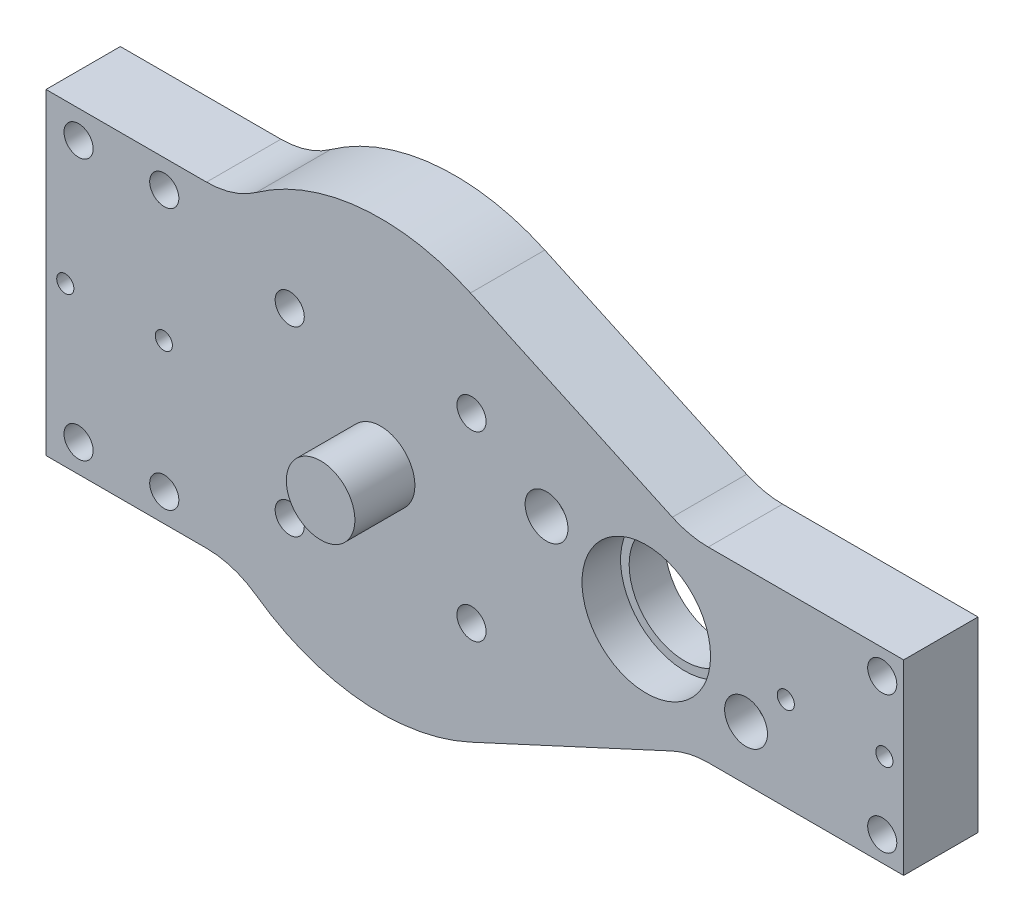
SolidWorks part; units mm, degrees
ref_plane "Front Plane" through (0, 0, 0) normal (0, 0, 1) x (1, 0, 0)
ref_plane "Top Plane" through (0, 0, 0) normal (0, 1, 0) x (1, 0, 0)
ref_plane "Right Plane" through (0, 0, 0) normal (1, 0, 0) x (0, 0, -1)
sketch "Sketch1" plane through (0, 0, 0) normal (0, 0, 1) x (1, 0, 0)
  line L0 (10.4839, 22.6956) -> (36.0323, 10.8939)
  line L1 (36.0323, -10.8939) -> (10.4839, -22.6956)
  circle A0 centre (0, 0) radius 22.215 construction
  circle A1 centre (31, 0) radius 10.2 construction
  arc A2 (10.4839, 22.6956) -> (10.4839, -22.6956) centre (0, 0) ccw
  arc A3 (36.0323, -10.8939) -> (36.0323, 10.8939) centre (31, 0) ccw
  dimension "D1" = 20.4
  dimension "D2" = 44.43
  dimension "D4" = 25
  dimension "D5" = 12
  dimension "D3" = 31
extrude "Boss-Extrude1" add sketch "Sketch1" along normal blind 4.5
sketch "Sketch2" plane through (0, 0, 4.5) normal (0, 0, 1) x (1, 0, 0)
  circle A0 centre (31, 0) radius 7.5
  dimension "D1" = 15
extrude "Cut-Extrude1" cut sketch "Sketch2" against normal through all
sketch "Sketch3" plane through (0, 0, 4.5) normal (0, 0, 1) x (1, 0, 0)
  circle A0 centre (0, 0) radius 4
  dimension "D1" = 8
extrude "Boss-Extrude2" add sketch "Sketch3" along normal blind 7
sketch "Sketch4" plane through (0, 0, 0) normal (0, 0, -1) x (-1, 0, 0)
  line L0 (-36.0323, 10.8939) -> (-56.0323, 10.8939)
  line L1 (-36.0323, -10.8939) -> (-56.0323, -10.8939)
  line L2 (-56.0323, -10.8939) -> (-56.0323, 10.8939)
  line L3 (22.5016, 10.8939) -> (42.5016, 10.8939)
  line L4 (42.5016, 10.8939) -> (42.5016, -10.8939)
  line L5 (42.5016, -10.8939) -> (22.5016, -10.8939)
  arc A0 (-10.4839, -22.6956) -> (-10.4839, 22.6956) centre (0, 0) ccw construction
  arc A1 (22.5016, -10.8939) -> (22.5016, 10.8939) centre (0, 0) ccw
  arc A2 (-36.0323, 10.8939) -> (-36.0323, -10.8939) centre (-31, 0) ccw construction
  arc A3 (-36.0323, 10.8939) -> (-36.0323, -10.8939) centre (-31, 0) ccw
  dimension "D1" = 20
  dimension "D2" = 20
extrude "Boss-Extrude3" add sketch "Sketch4" against normal up to surface (4.5 mm away) up to face at (4, 0, 4.5)
fillet "Fillet1" radius 10 4 edges at (-42.5016, 10.8939, 2.25) (-42.5016, -10.8939, 2.25) (56.0323, -10.8939, 2.25) (56.0323, 10.8939, 2.25)
sketch "Sketch8" plane through (0, 0, 4.5) normal (0, 0, 1) x (1, 0, 0)
  line L0 (56.0323, 0.8939) -> (56.0323, -0.8939) construction
  line L2 (56.0323, 0.8939) -> (56.0323, -0.8939)
  line L3 (55.4014, -4.3896) -> (55.4014, 4.3896)
  line L4 (-42.5016, -0.8939) -> (-42.5016, 0.8939) construction
  line L6 (-42.5016, -0.8939) -> (-42.5016, 0.8939)
  line L7 (-41.8707, 4.3896) -> (-41.8707, -4.3896)
  arc A0 (56.0323, 0.8939) -> (46.0323, 10.8939) centre (46.0323, 0.8939) ccw construction
  arc A1 (46.0323, -10.8939) -> (56.0323, -0.8939) centre (46.0323, -0.8939) ccw construction
  arc A2 (56.0323, 0.8939) -> (55.4014, 4.3896) centre (46.0323, 0.8939) ccw
  arc A3 (55.4014, -4.3896) -> (56.0323, -0.8939) centre (46.0323, -0.8939) ccw
  arc A4 (-32.5016, 10.8939) -> (-42.5016, 0.8939) centre (-32.5016, 0.8939) ccw construction
  arc A5 (-42.5016, -0.8939) -> (-32.5016, -10.8939) centre (-32.5016, -0.8939) ccw construction
  arc A6 (-41.8707, 4.3896) -> (-42.5016, 0.8939) centre (-32.5016, 0.8939) ccw
  arc A7 (-42.5016, -0.8939) -> (-41.8707, -4.3896) centre (-32.5016, -0.8939) ccw
extrude "Cut-Extrude4" cut sketch "Sketch8" against normal through all
sketch "Sketch9" plane through (0, 0, 4.5) normal (0, 0, 1) x (1, 0, 0)
  circle A0 centre (0, 0) radius 15 construction
  circle A1 centre (-10.6066, 10.6066) radius 1
  circle A2 centre (10.6066, 10.6066) radius 1
  circle A3 centre (10.6066, -10.6066) radius 1
  circle A4 centre (-10.6066, -10.6066) radius 1
  point P14 (0, 0)
  dimension "D1" = 30
  dimension "D2" = 2
  dimension "D3" = 4
extrude "Cut-Extrude5" cut sketch "Sketch9" against normal through all
sketch "Sketch10" plane through (0, 0, 4.5) normal (0, 0, 1) x (1, 0, 0)
  circle A0 centre (-10.6066, 10.6066) radius 1.7
  circle A1 centre (10.6066, 10.6066) radius 1.7
  circle A2 centre (10.6066, -10.6066) radius 1.7
  circle A3 centre (-10.6066, -10.6066) radius 1.7
  dimension "D1" = 3.4
extrude "Cut-Extrude6" cut sketch "Sketch10" against normal blind 2.4
sketch "Sketch11" plane through (0, 0, 0) normal (0, 0, -1) x (-1, 0, 0)
  line L0 (-40.9602, 14.6461) -> (-73.6718, 18.9155)
  line L1 (-73.6718, 18.9155) -> (-68.6403, -15.6759)
  line L2 (-68.6403, -15.6759) -> (-41.445, -13.2122)
  arc A0 (-40.9602, 14.6461) -> (-41.445, -13.2122) centre (0, 0) ccw
  dimension "D1" = 87
extrude "Cut-Extrude7" cut sketch "Sketch11" against normal up to surface (4.5 mm away) up to face at (-8.9066, -10.6066, 4.5)
fillet "Fillet2" radius 10 2 edges at (42.1138, -10.8939, 2.25) (42.1138, 10.8939, 2.25)
sketch "Sketch12" plane through (0, 0, 4.5) normal (0, 0, 1) x (1, 0, 0)
  line L0 (-22.5016, 10.8939) -> (-42.5927, 14.8195)
  line L1 (-42.5927, 14.8195) -> (-48.1481, -13.6126)
  line L2 (-48.1481, -13.6126) -> (-27.4273, -14.3153)
  line L3 (-27.4273, -14.3153) -> (-22.5016, -10.8939)
  arc A0 (-22.5016, 10.8939) -> (-22.5016, -10.8939) centre (0, 0) ccw
extrude "Cut-Extrude8" cut sketch "Sketch12" against normal through all
sketch "Sketch23" plane through (0, 0, 0) normal (0, 0, -1) x (-1, 0, 0)
  line L2 (-36.0323, -10.8939) -> (-10.4839, -22.6956)
  line L3 (-10.4839, 22.6956) -> (-36.0323, 10.8939)
  line L4 (-36.0323, -10.8939) -> (-10.4839, -22.6956)
  line L5 (-10.4839, 22.6956) -> (-36.0323, 10.8939)
  circle A0 centre (-10.6066, -10.6066) radius 1 construction
  circle A1 centre (10.6066, -10.6066) radius 1 construction
  circle A2 centre (10.6066, 10.6066) radius 1 construction
  circle A3 centre (-10.6066, 10.6066) radius 1 construction
  arc A4 (-10.4839, -22.6956) -> (-10.4839, 22.6956) centre (0, 0) ccw
  arc A5 (-36.0323, 10.8939) -> (-43.4709, 1.5916) centre (-33.4776, 1.2257) ccw
  arc A6 (-43.4709, 1.5916) -> (-43.4709, -1.5916) centre (0, 0) ccw
  arc A7 (-43.4709, -1.5916) -> (-36.0323, -10.8939) centre (-33.4776, -1.2257) ccw
  arc A8 (-10.4839, -22.6956) -> (-10.4839, 22.6956) centre (0, 0) ccw
  arc A9 (-36.0323, 10.8939) -> (-43.4709, 1.5916) centre (-33.4776, 1.2257) ccw
  arc A10 (-43.4709, 1.5916) -> (-43.4709, -1.5916) centre (0, 0) ccw
  arc A11 (-43.4709, -1.5916) -> (-36.0323, -10.8939) centre (-33.4776, -1.2257) ccw
  circle A12 centre (-10.6066, -10.6066) radius 1
  circle A13 centre (10.6066, -10.6066) radius 1
  circle A14 centre (10.6066, 10.6066) radius 1
  circle A15 centre (-10.6066, 10.6066) radius 1
  circle A16 centre (-31, 0) radius 6.5
  dimension "D2" = 13
  dimension "D1" = 0
extrude "Boss-Extrude6" add sketch "Sketch23" along normal blind 4.175
sketch "Sketch24" plane through (0, 0, -4.175) normal (0, 0, -1) x (-1, 0, 0)
  line L0 (-10.6066, 10.6066) -> (10.6066, 10.6066) construction
ref_axis "Axis1" through (10.6066, 10.6066, -4.175) along (-1, 0, 0)
sketch "Sketch25" plane through (0, 0, -4.175) normal (0, 0, -1) x (-1, 0, 0)
  line L1 (-36.0323, 10.8939) -> (-56.0323, 10.8939)
  line L3 (-36.0323, -10.8939) -> (-56.0323, -10.8939)
  line L4 (-56.0323, 10.8939) -> (-56.0323, -10.8939)
  arc A0 (-43.4709, -1.5916) -> (-36.0323, -10.8939) centre (-33.4776, -1.2257) ccw construction
  arc A1 (-43.4709, 1.5916) -> (-43.4709, -1.5916) centre (0, 0) ccw construction
  arc A2 (-36.0323, 10.8939) -> (-43.4709, 1.5916) centre (-33.4776, 1.2257) ccw construction
  arc A3 (-43.4709, -1.5916) -> (-36.0323, -10.8939) centre (-33.4776, -1.2257) ccw
  arc A4 (-43.4709, 1.5916) -> (-43.4709, -1.5916) centre (0, 0) ccw
  arc A5 (-36.0323, 10.8939) -> (-43.4709, 1.5916) centre (-33.4776, 1.2257) ccw
  dimension "D1" = 20
extrude "Boss-Extrude7" add sketch "Sketch25" against normal up to surface (8.675 mm away) up to face at (24.5985, 0, 4.5)
sketch "Sketch26" plane through (0, 0, 4.5) normal (0, 0, 1) x (1, 0, 0)
  line L0 (36.0323, 10.8939) -> (56.0323, 10.8939) construction
  line L1 (56.0323, -10.8939) -> (47.0323, -10.8939)
  line L2 (56.0323, -10.8939) -> (56.0323, 10.8939)
  line L3 (56.0323, 10.8939) -> (47.0323, 10.8939)
  line L4 (47.0323, -10.8939) -> (47.0323, 10.8939)
  dimension "D1" = 9
extrude "Boss-Extrude8" add sketch "Sketch26" along normal blind 33
sketch "Sketch27" plane through (56.0323, 0, 0) normal (1, 0, 0) x (0, 0, -1)
  circle A0 centre (-29.5, 0) radius 5
extrude "Cut-Extrude9" cut sketch "Sketch27" against normal up to next
sketch "Sketch28" plane through (0, 0, -4.175) normal (0, 0, -1) x (-1, 0, 0)
  line L1 (16.8152, 18.5) -> (52.8559, 18.5)
  line L3 (16.8152, -18.5) -> (52.8559, -18.5)
  line L4 (0, 0) -> (56, 0) construction
  line L5 (56, 0) -> (25.875, 18.5) construction
  line L6 (56, 0) -> (31.6196, -18.5) construction
  line L7 (52.8559, -18.5) -> (25, 0) construction
  line L8 (25, 0) -> (52.8559, 18.5) construction
  line L9 (52.8559, 18.5) -> (52.8559, -18.5)
  arc A0 (52.8559, -18.5) -> (52.8559, 18.5) centre (0, 0) ccw construction
  arc A2 (-10.4839, -22.6956) -> (-10.4839, 22.6956) centre (0, 0) ccw construction
  arc A3 (16.8152, -18.5) -> (16.8152, 18.5) centre (0, 0) ccw
  dimension "D1" = 112
  dimension "D3" = 37
extrude "Boss-Extrude9" add sketch "Sketch28" against normal up to surface (8.675 mm away) up to face at (38.5, 0, 4.5)
sketch "Sketch29" plane through (0, 0, 4.5) normal (0, 0, 1) x (1, 0, 0)
  line L0 (-52.8559, 18.5) -> (-34.8356, 18.5)
  line L1 (-52.8559, 18.5) -> (-52.8559, -18.5)
  line L2 (-52.8559, -18.5) -> (-34.8356, -18.5)
  line L3 (-16.8152, -18.5) -> (-52.8559, -18.5) construction
  line L4 (-52.8559, 18.5) -> (-16.8152, 18.5) construction
  line L5 (-50.8559, 16.5) -> (-50.8559, -16.5)
  line L6 (-50.8559, 16.5) -> (-52.8559, 18.5) construction
  line L7 (-50.8559, -16.5) -> (-52.8559, -18.5) construction
  line L8 (-50.8559, 16.5) -> (-34.8356, 16.5)
  line L9 (-34.8356, 16.5) -> (-34.8356, 18.5)
  line L10 (-34.8356, -18.5) -> (-34.8356, -16.5)
  line L11 (-34.8356, -16.5) -> (-50.8559, -16.5)
  dimension "D1" = 33
  dimension "D2" = 2
extrude "Boss-Extrude10" add sketch "Sketch29" along normal blind 105
fillet "Fillet4" radius 10 4 edges at (36.0323, 10.8939, 0.1625) (36.0323, -10.8939, 0.1625) (-16.8152, 18.5, 0.1625) (-16.8152, -18.5, 0.1625)
sketch "Sketch30" plane through (56.0323, 0, 0) normal (1, 0, 0) x (0, 0, -1)
  line L0 (-34.1928, 1.7255) -> (-34.8273, 0)
  line L1 (-34.8273, 0) -> (-34.1928, -1.7255)
  line L2 (-34.5, 0) -> (-34.8273, 0) construction
  circle A0 centre (-29.5, 0) radius 5 construction
  arc A1 (-34.1928, 1.7255) -> (-34.1928, -1.7255) centre (-29.5, 0) ccw
extrude "Cut-Extrude10" cut sketch "Sketch30" against normal up to surface (9 mm away) up to face at (47.0323, 0, 24.5)
sketch "Sketch31" plane through (0, 0, 4.5) normal (0, 0, 1) x (1, 0, 0)
  line L0 (-48.7944, 12.5) -> (-50.8559, 16.5) construction
  line L1 (-48.7944, 12.5) -> (-36.7944, 12.5)
  line L2 (-48.7944, 12.5) -> (-48.7944, -12.5)
  line L3 (-48.7944, -12.5) -> (-36.7944, -12.5)
  line L4 (-36.7944, 12.5) -> (-36.7944, -12.5)
  line L5 (-48.7944, -12.5) -> (-50.8559, -16.5) construction
  dimension "D1" = 25
  dimension "D2" = 12
  dimension "D3" = 4.5
extrude "Cut-Extrude11" cut sketch "Sketch31" against normal through all
sketch "Sketch32" plane through (0, 0, 4.5) normal (0, 0, 1) x (1, 0, 0)
  line L0 (-34.8356, 18.5) -> (-34.8356, 16.5)
  line L1 (-34.8356, 16.5) -> (-27.7321, 16.5)
  line L2 (-27.7321, 16.5) -> (-27.7321, -16.5)
  line L3 (-27.7321, -16.5) -> (-34.8356, -16.5)
  line L4 (-34.8356, -16.5) -> (-34.8356, -18.5)
  line L5 (-34.8356, -18.5) -> (-27.5759, -18.5)
  line L6 (-20.3162, -18.5) -> (-34.8356, -18.5) construction
  line L7 (-27.5759, -18.5) -> (-27.5759, 18.5)
  line L8 (-34.8356, 18.5) -> (-20.3162, 18.5) construction
  line L9 (-27.5759, 18.5) -> (-34.8356, 18.5)
extrude "Boss-Extrude11" add sketch "Sketch32" along normal blind 10
sketch "Sketch33" plane through (-27.5759, 0, 0) normal (1, 0, 0) x (0, 0, -1)
  line L0 (-4.5, -22.6956) -> (-4.5, -11.8156) construction
  line L1 (-14.5, 16.5) -> (-4.5, 16.5)
  line L2 (-14.5, 16.5) -> (-14.5, -16.5)
  line L3 (-14.5, -16.5) -> (-4.5, -16.5)
  line L4 (-4.5, 16.5) -> (-4.5, -16.5)
  line L5 (-109.5, -16.5) -> (-4.5, -16.5) construction
extrude "Cut-Extrude12" cut sketch "Sketch33" against normal up to next
sketch "Sketch34" plane through (-50.8559, 0, 0) normal (1, 0, 0) x (0, 0, -1)
  line L0 (-109.5, 16.5) -> (-109.5, 18.5) construction
  line L1 (-109.5, 17.5) -> (-4.5, 17.5)
  line L2 (-109.5, 17.5) -> (-109.5, -17.5)
  line L3 (-109.5, -17.5) -> (-4.5, -17.5)
  line L4 (-4.5, 17.5) -> (-4.5, -17.5)
  line L5 (-4.5, -18.5) -> (-4.5, -16.5) construction
extrude "Cut-Extrude13" cut sketch "Sketch34" along normal up to surface (23.28 mm away) up to face at (-27.5759, -17.5, 9.5)
sketch "Sketch35" plane through (56.0323, 0, 0) normal (1, 0, 0) x (0, 0, -1)
  circle A0 centre (-29.5, 0) radius 5.5
  dimension "D1" = 11
extrude "Cut-Extrude14" [suppressed] cut sketch "Sketch35" against normal up to next
sketch "Sketch36" [suppressed] plane through (56.0323, 0, 0) normal (1, 0, 0) x (0, 0, -1)
  line L0 (-34.3284, 2.6337) -> (-35.765, 0)
  line L1 (-35.765, 0) -> (-34.3284, -2.6337)
  line L2 (-35.765, 0) -> (0, 0) construction
  circle A0 centre (-29.5, 0) radius 5.5 construction
  arc A1 (-34.3284, -2.6337) -> (-34.3284, 2.6337) centre (-29.5, 0) cw
  dimension "D1" = 3
extrude "Cut-Extrude15" [suppressed] cut sketch "Sketch36" against normal up to next
sketch "Sketch37" plane through (0, 0, 37.5) normal (0, 0, 1) x (1, 0, 0)
  line L0 (47.0323, -10.8939) -> (56.0323, -10.8939) construction
  line L1 (47.0323, 10.8939) -> (49.0323, 10.8939)
  line L2 (47.0323, 10.8939) -> (47.0323, -10.8939)
  line L3 (47.0323, -10.8939) -> (49.0323, -10.8939)
  line L4 (49.0323, 10.8939) -> (49.0323, -10.8939)
  dimension "D1" = 2
extrude "Cut-Extrude16" cut sketch "Sketch37" against normal up to surface (33 mm away) up to face at (-1.2525, 0, 4.5)
sketch "Sketch38" plane through (0, 0, 4.5) normal (0, 0, 1) x (1, 0, 0)
  line L0 (19.3604, 4.5575) -> (42.6396, -4.5575) construction
  circle A0 centre (31, 0) radius 12.5 construction
  circle A1 centre (19.3604, 4.5575) radius 1.5
  circle A2 centre (42.6396, -4.5575) radius 1.5
  dimension "D1" = 25
  dimension "D2" = 3
extrude "Cut-Extrude17" cut sketch "Sketch38" against normal blind 10
sketch "Sketch39" plane through (0, 0, 4.5) normal (0, 0, 1) x (1, 0, 0)
  circle A0 centre (19.3604, 4.5575) radius 2.5
  circle A1 centre (42.6396, -4.5575) radius 2.5
  dimension "D1" = 5
extrude "Cut-Extrude18" cut sketch "Sketch39" against normal blind 3.5
sketch "Sketch40" plane through (0, 0, 4.5) normal (0, 0, 1) x (1, 0, 0)
  line L1 (-52.8559, 18.5) -> (-27.5759, 18.5)
  line L2 (-52.8559, 18.5) -> (-52.8559, -18.5)
  line L3 (-52.8559, -18.5) -> (-27.5759, -18.5)
  line L4 (-27.5759, 18.5) -> (-27.5759, -18.5)
extrude "Cut-Extrude19" cut sketch "Sketch40" along normal blind 133.5
sketch "Sketch41" plane through (0, 0, 4.5) normal (0, 0, 1) x (1, 0, 0)
  line L1 (-48.7944, 12.5) -> (-36.7944, 12.5)
  line L2 (-48.7944, 12.5) -> (-48.7944, -12.5)
  line L3 (-48.7944, -12.5) -> (-36.7944, -12.5)
  line L4 (-36.7944, 12.5) -> (-36.7944, -12.5)
extrude "Boss-Extrude12" add sketch "Sketch41" against normal up to surface (8.675 mm away) up to face at (17.8604, 4.5575, -4.175)
sketch "Sketch42" plane through (0, 0, 4.5) normal (0, 0, 1) x (1, 0, 0)
  line L0 (-20.3162, -18.5) -> (-52.8559, -18.5) construction
  line L1 (-52.8559, 18.5) -> (-39.0453, 18.5)
  line L2 (-52.8559, 18.5) -> (-52.8559, -18.5)
  line L3 (-52.8559, -18.5) -> (-39.0453, -18.5)
  line L4 (-39.0453, 18.5) -> (-39.0453, -18.5)
extrude "Cut-Extrude20" cut sketch "Sketch42" against normal through all
sketch "Sketch43" plane through (0, 0, 4.5) normal (0, 0, 1) x (1, 0, 0)
  line L0 (-39.0453, 18.5) -> (-35.2453, 15.2504) construction
  line L1 (-35.2453, 15.2504) -> (-25.2453, 15.2504) construction
  line L2 (-35.2453, 15.2504) -> (-35.2453, -15.2504) construction
  line L3 (-35.2453, -15.2504) -> (-25.2453, -15.2504) construction
  line L4 (-25.2453, 15.2504) -> (-25.2453, -15.2504) construction
  line L5 (-35.2453, -15.2504) -> (-39.0453, -18.5) construction
  line L7 (-39.0453, -18.5) -> (-39.0453, 18.5) construction
  circle A0 centre (-35.2453, 15.2504) radius 1
  circle A1 centre (-35.2453, -15.2504) radius 1
  circle A2 centre (-25.2453, 15.2504) radius 1
  circle A3 centre (-25.2453, -15.2504) radius 1
  dimension "D1" = 2
  dimension "D2" = 5
  dimension "D3" = 10
  dimension "D4" = 3.8
extrude "Cut-Extrude21" cut sketch "Sketch43" against normal through all
sketch "Sketch44" plane through (0, 0, 4.5) normal (0, 0, 1) x (1, 0, 0)
  circle A0 centre (-35.2453, 15.2504) radius 1.7
  circle A1 centre (-25.2453, 15.2504) radius 1.7
  circle A2 centre (-35.2453, -15.2504) radius 1.7
  circle A3 centre (-25.2453, -15.2504) radius 1.7
  circle A4 centre (-10.6066, 10.6066) radius 1.7 construction
extrude "Cut-Extrude22" cut sketch "Sketch44" against normal blind 3
sketch "Sketch45" plane through (0, 0, -4.175) normal (0, 0, -1) x (-1, 0, 0)
  line L0 (-56.0323, -10.8939) -> (-38.2303, -10.8939) construction
  line L1 (-56.0323, 10.8939) -> (-61.0323, 10.8939)
  line L2 (-56.0323, 10.8939) -> (-56.0323, -10.8939)
  line L3 (-56.0323, -10.8939) -> (-61.0323, -10.8939)
  line L4 (-61.0323, 10.8939) -> (-61.0323, -10.8939)
  line L5 (-61.0323, 10.8939) -> (-58.5323, 8) construction
  line L6 (-58.5323, 8) -> (-58.5323, -8) construction
  line L7 (-58.5323, -8) -> (-61.0323, -10.8939) construction
  line L8 (-58.5323, -8) -> (-56.0323, -10.8939) construction
  circle A0 centre (-58.5323, 8) radius 1
  circle A1 centre (-58.5323, -8) radius 1
  dimension "D3" = 2
  dimension "D1" = 5
  dimension "D2" = 16
extrude "Boss-Extrude13" add sketch "Sketch45" against normal up to surface (8.675 mm away) up to face at (-23.5453, 15.2504, 4.5)
sketch "Sketch46" plane through (0, 0, 4.5) normal (0, 0, 1) x (1, 0, 0)
  circle A0 centre (58.5323, 8) radius 1.7
  circle A1 centre (58.5323, -8) radius 1.7
  circle A2 centre (10.6066, -10.6066) radius 1.7 construction
extrude "Cut-Extrude23" cut sketch "Sketch46" against normal blind 3
fillet "Fillet5" radius 1 2 edges at (56.0323, 0, 4.5) (49.0323, 0, 4.5)
sketch "Sketch47" plane through (0, 0, 4.5) normal (0, 0, 1) x (1, 0, 0)
  line L1 (77.9328, -23.2668) -> (28.4841, -23.2668)
  line L2 (77.9328, -23.2668) -> (77.9328, 23.2668)
  line L3 (77.9328, 23.2668) -> (28.4841, 23.2668)
  line L4 (28.4841, -23.2668) -> (28.4841, 23.2668)
  line L5 (77.9328, -23.2668) -> (28.4841, 23.2668) construction
  line L6 (77.9328, 23.2668) -> (28.4841, -23.2668) construction
  point P0 (53.2084, 0)
extrude "Cut-Extrude25" cut sketch "Sketch47" along normal up to surface (33 mm away) up to face at (52.5323, 0, 37.5)
ref_plane "Plane1" through (0, 0, 0.1625) normal (0, 0, -1) x (-1, 0, 0)
sketch "Sketch51" plane through (0, 0, -4.175) normal (0, 0, -1) x (-1, 0, 0)
  line L0 (39.0453, 0) -> (-72.4265, 0) construction
  line L1 (39.0453, -18.5) -> (39.0453, 18.5) construction
  line L2 (-61.0323, 10.8939) -> (-61.0323, -10.8939) construction
  circle A0 centre (36.7953, 0) radius 1
  circle A1 centre (25.2953, 0) radius 1
  circle A2 centre (-58.7823, 0) radius 1
  circle A3 centre (-47.2823, 0) radius 1
  dimension "D2" = 2
  dimension "D4" = 2.25
  dimension "D5" = 11.5
  dimension "D1" = 2.25
  dimension "D3" = 11.5
extrude "Cut-Extrude26" cut sketch "Sketch51" against normal through all
sketch "Sketch52" plane through (0, 0, -4.175) normal (0, 0, -1) x (-1, 0, 0)
  circle A0 centre (36.7953, 0) radius 1.675
  circle A1 centre (25.2953, 0) radius 1.675
  circle A2 centre (-47.2823, 0) radius 1.675
  circle A3 centre (-58.7823, 0) radius 1.675
  dimension "D1" = 3.35
extrude "Cut-Extrude27" cut sketch "Sketch52" against normal blind 5
